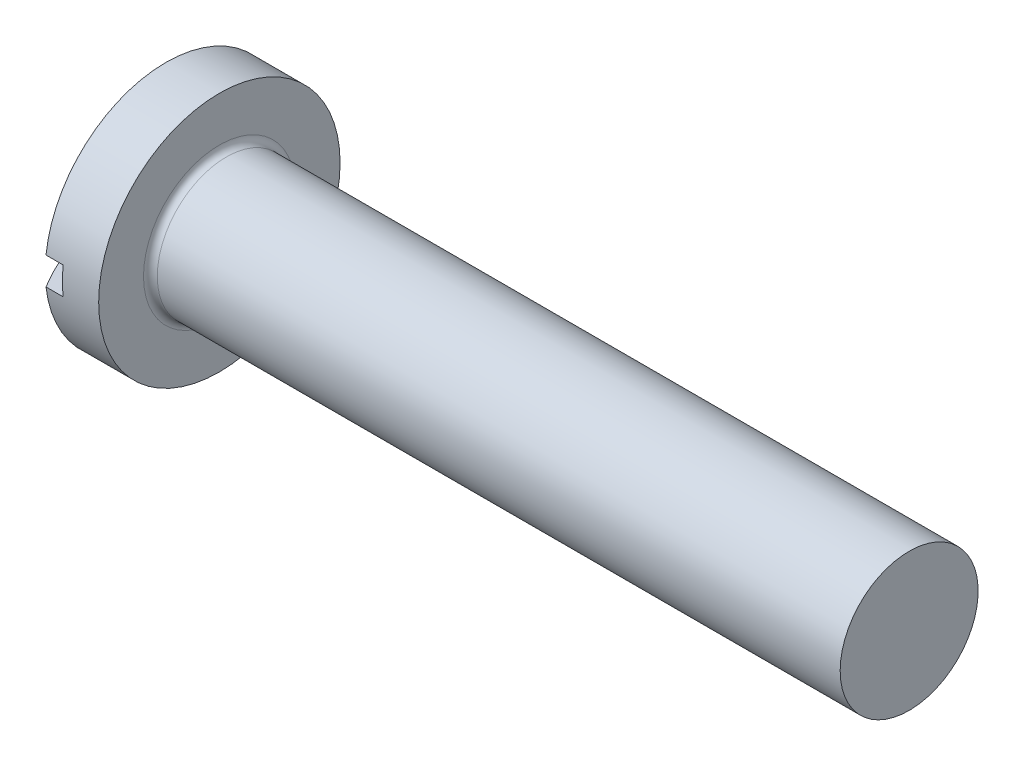
SolidWorks part; units mm, degrees
ref_plane "Front Plane" through (0, 0, 0) normal (0, 0, 1) x (1, 0, 0)
ref_plane "Top Plane" through (0, 0, 0) normal (0, 1, 0) x (1, 0, 0)
ref_plane "Right Plane" through (0, 0, 0) normal (1, 0, 0) x (0, 0, -1)
sketch "BodySke" plane through (0, 0, 0) normal (0, 0, 1) x (1, 0, 0)
  line L0 (0, 0) -> (120.5141, 0) construction
  line L1 (0, 0) -> (0, 50.5629) construction
  line L2 (5.1, 7) -> (5.1, 4)
  line L3 (5.1, 4) -> (45.1, 4)
  line L4 (45.1, 4) -> (45.1, 0)
  line L5 (0, 0) -> (45.1, 0)
  line L6 (5.1, 7) -> (2, 7)
  line L7 (6.35, 9.2217) -> (6.35, -4.3786) construction
  line L8 (15.1, 9.5609) -> (15.1, -6.7938) construction
  arc A0 (0, 0) -> (2, 7) centre (13.25, 0) cw
  point P14 (45.1, 3.3095)
  dimension "Thread_minor" = 6.619
  dimension "Head_height" = 3.1
  dimension "Advance" = 1.25
revolve "BaseBody" add sketch "BodySke" angle 360 about L0
cosmetic thread "ThreadCosmetic" [suppressed] parameters "Thread_minor"=6.619
fillet "Fillet1" radius 0.4 1 edges at (5.1, 0, 4)
sketch "SlotSke" plane through (0, 0, 0) normal (1, 0, 0) x (0, 0, -1)
  line L1 (7, 0.8) -> (-7, 0.8)
  line L2 (7, 0.8) -> (7, -0.8)
  line L3 (7, -0.8) -> (-7, -0.8)
  line L4 (-7, 0.8) -> (-7, -0.8)
  dimension "D1" = 14
  dimension "D2" = 7
  dimension "D4" = 0.8
extrude "Slot" cut sketch "SlotSke" along normal blind 3
sketch "ThdSchSke" plane through (0, 0, 0) normal (0, 0, 1) x (1, 0, 0)
  line L0 (0, 0) -> (54.7976, 0) construction
  line L1 (44.7013, 4.7973) -> (44.7013, 4)
  line L2 (44.7013, 4.7973) -> (45.4987, 4.7973)
  line L3 (45.4987, 4.7973) -> (45.4987, 4)
  line L4 (45.4987, 4) -> (45.1, 3.3095)
  line L5 (45.1, 3.3095) -> (44.7013, 4)
  line L6 (5.1, 4) -> (45.1, 4) construction
revolve "ThreadSchematic" [suppressed] cut sketch "ThdSchSke" angle 360 about L0
pattern_linear "ThdSchPat" [suppressed] count 24 along (-1, 0, 0) of bodies 103
equation "\"Thread_minor@ThreadCosmetic\" = \"Thread_minor@BodySke\""
equation "\"D1@SlotSke\" = \"Head_dia@BodySke\""
equation "\"D2@SlotSke\" = \"D1@SlotSke\" / 2"
equation "\"D4@SlotSke\" = \"Slot_width@SlotSke\" / 2"
equation "\"Advance@ThdSchPat\" = \"Advance@BodySke\""
equation "\"D1@ThdSchPat\" =  int( \"Thread_length@BodySke\" / \"Advance@BodySke\" ) "
